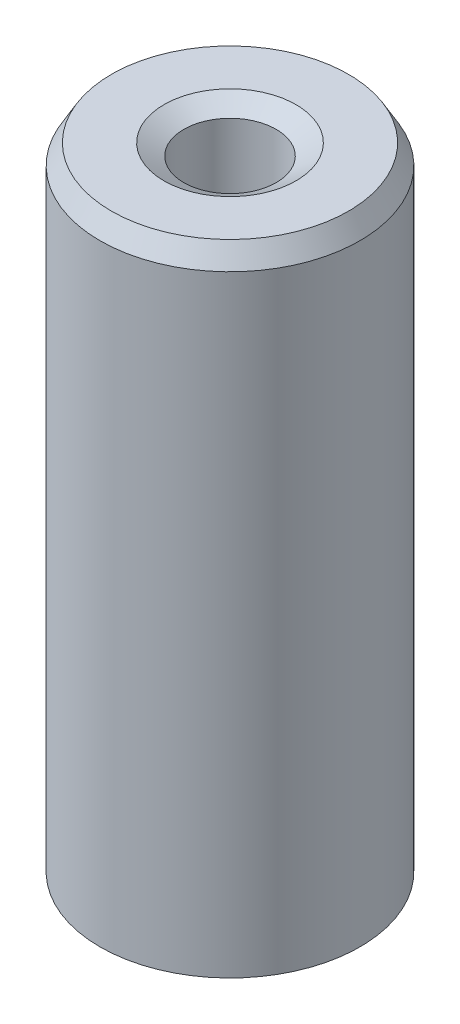
SolidWorks part; units mm, degrees
ref_plane "Front Plane" through (0, 0, 0) normal (0, 0, 1) x (1, 0, 0)
ref_plane "Top Plane" through (0, 0, 0) normal (0, 1, 0) x (1, 0, 0)
ref_plane "Right Plane" through (0, 0, 0) normal (1, 0, 0) x (0, 0, -1)
sketch "Sketch1" plane through (0, 0, 0) normal (0, 1, 0) x (1, 0, 0)
  circle A0 centre (0, 0) radius 12.5
  dimension "SLEEVE_OD" = 25
extrude "Boss-Extrude1" add sketch "Sketch1" along normal blind 61.8129
sketch "Sketch2" plane through (0, 0, 0) normal (0, 1, 0) x (1, 0, 0)
  circle A0 centre (0, 0) radius 4.4406
  dimension "BORE_D" = 8.8812
extrude "Cut-Extrude1" cut sketch "Sketch2" along normal through all
chamfer "Chamfer1" distance 1.9085 angle 30.007 4 edges at (0, 61.8129, 4.4406) (0, 0, 4.4406) (0, 0, 12.5) (0, 61.8129, 12.5) first distance on face at (0, 61.8129, 4.4406) first distance on face at (0, 0, 4.4406) first distance on face at (0, 61.8129, 12.5)
